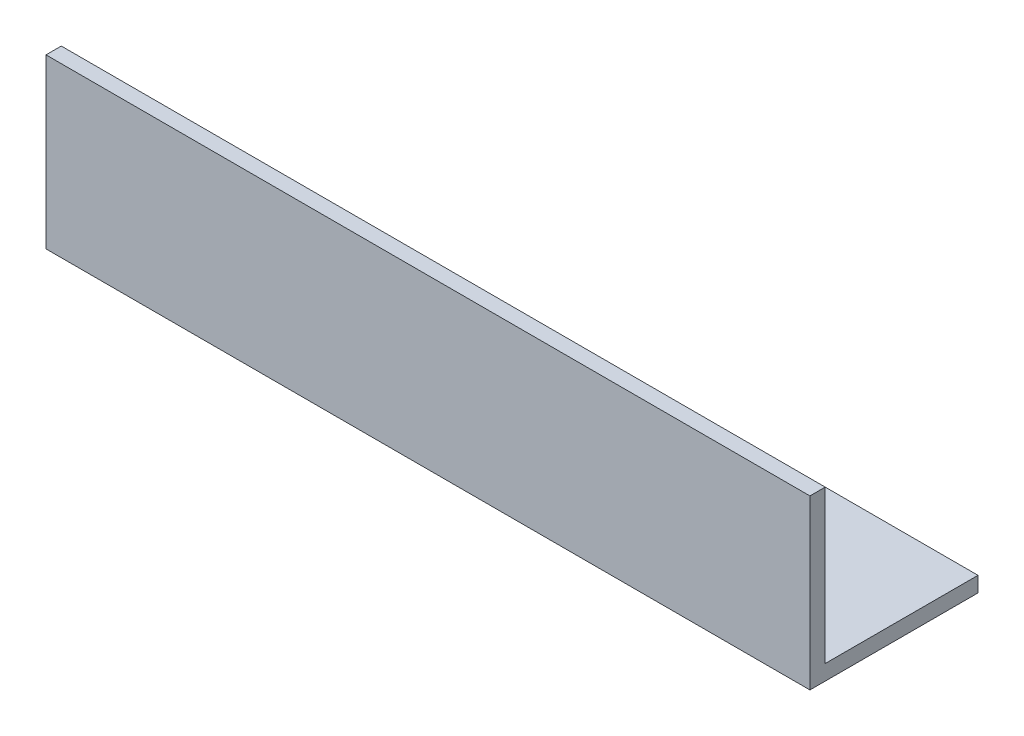
SolidWorks part; units mm, degrees
ref_plane "Спереди" through (0, 0, 0) normal (0, 0, 1) x (1, 0, 0)
ref_plane "Сверху" through (0, 0, 0) normal (0, 1, 0) x (1, 0, 0)
ref_plane "Справа" through (0, 0, 0) normal (1, 0, 0) x (0, 0, -1)
sketch "Эскиз1" plane through (0, 0, 0) normal (1, 0, 0) x (0, 0, -1)
  line L0 (0, 0) -> (0, 30)
  line L1 (0, 0) -> (30, 0)
extrude "Вытянуть-Тонкостенный1" add sketch "Эскиз1" along normal blind 150 thin thin type one direction wall 3
sketch "Эскиз2" plane through (0, -3, 0) normal (0, -1, 0) x (1, 0, 0)
  line L0 (75, -35.357) -> (75, 2.5686) construction
  circle A0 centre (130, -9) radius 5
  circle A1 centre (100, -9) radius 5
  circle A2 centre (50, -9) radius 5
  circle A3 centre (20, -9) radius 5
  dimension "D1" = 2
extrude "Вырез-Вытянуть1" cut sketch "Эскиз2" against normal through all
